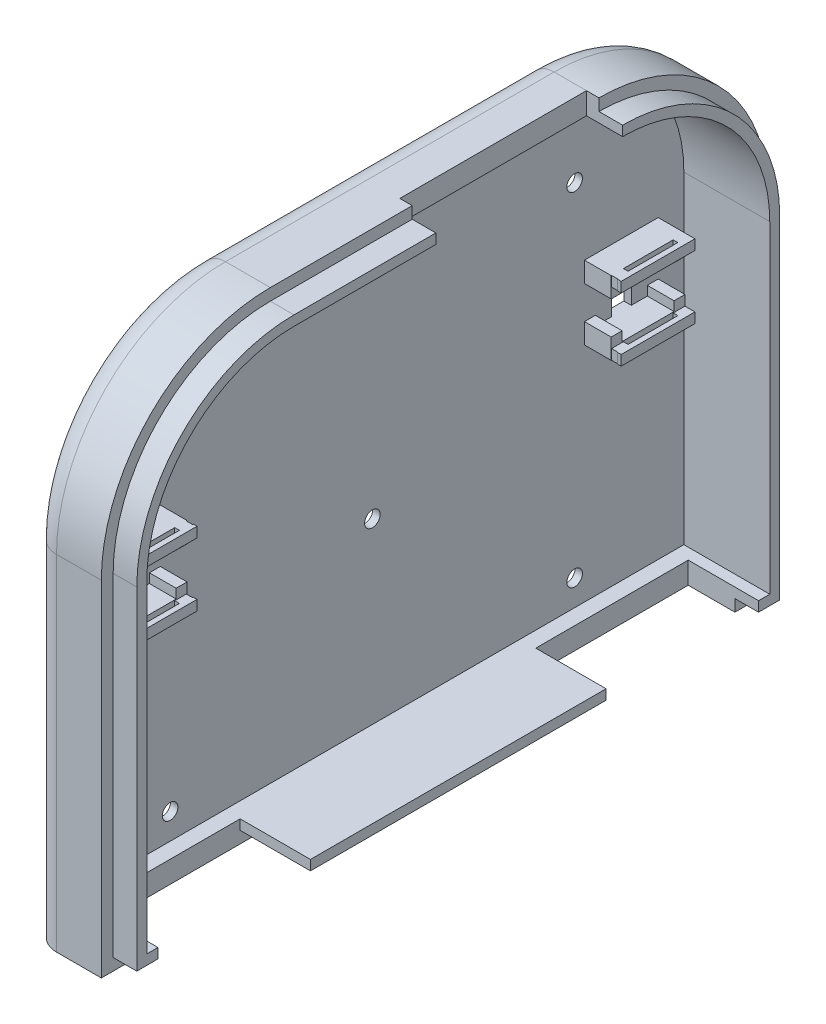
SolidWorks part; units mm, degrees
ref_plane "Front Plane" through (0, 0, 0) normal (0, 0, 1) x (1, 0, 0)
ref_plane "Top Plane" through (0, 0, 0) normal (0, 1, 0) x (1, 0, 0)
ref_plane "Right Plane" through (0, 0, 0) normal (1, 0, 0) x (0, 0, -1)
sketch "Sketch1" plane through (0, 0, 0) normal (1, 0, 0) x (0, 0, -1)
  line L0 (-52.8, 94.65) -> (52.8, 94.65)
  line L1 (-107.1, 40.35) -> (-107.1, -40.35)
  line L2 (-70, -70.35) -> (70, -70.35)
  line L3 (107.1, 40.35) -> (107.1, -40.35)
  line L4 (107.1, 0) -> (-107.1, 0) construction
  line L5 (0, 94.65) -> (0, -70.35) construction
  line L11 (107.1, -40.35) -> (107.1, -70.35)
  line L12 (107.1, -70.35) -> (70, -70.35)
  line L13 (-83.2, 28.3) -> (-76.8, 28.3)
  line L14 (-83.2, 28.3) -> (-83.2, 11.7)
  line L15 (-83.2, 11.7) -> (-76.8, 11.7)
  line L16 (-76.8, 28.3) -> (-76.8, 11.7)
  line L17 (-83.2, 28.3) -> (-76.8, 11.7) construction
  line L18 (-83.2, 11.7) -> (-76.8, 28.3) construction
  line L19 (76.8, 28.3) -> (83.2, 28.3)
  line L20 (76.8, 28.3) -> (76.8, 11.7)
  line L21 (76.8, 11.7) -> (83.2, 11.7)
  line L22 (83.2, 28.3) -> (83.2, 11.7)
  line L23 (76.8, 28.3) -> (83.2, 11.7) construction
  line L24 (76.8, 11.7) -> (83.2, 28.3) construction
  line L25 (80, 20) -> (-80, 20)
  line L27 (-107.1, -40.35) -> (-107.1, -70.35)
  line L28 (-107.1, -70.35) -> (-70, -70.35)
  arc A0 (52.8, 94.65) -> (107.1, 40.35) centre (52.8, 40.35) cw
  arc A1 (-52.8, 94.65) -> (-107.1, 40.35) centre (-52.8, 40.35) ccw
  point P16 (0, 0)
  point P17 (-80, 20)
  point P32 (80, 20)
  point P39 (-80, 20)
  point P40 (0, 20)
  dimension "D4" = 54.3
  dimension "D2" = 165
  dimension "D3" = 214.2
  dimension "D5" = 140
  dimension "D6" = 30
  dimension "D7" = 160
  dimension "D8" = 6.4
  dimension "D9" = 16.6
  dimension "D10" = 6.4
  dimension "D11" = 16.6
  dimension "D12" = 20
extrude "Boss-Extrude1" add sketch "Sketch1" along normal blind 2.4 contours L2 L3 A0 L0 A1 L1 L19 L22 L21 L20 L13 L16 L15 L14 region at (0, 9.471, 0)
sketch "Sketch9" plane through (2.4, 0, 0) normal (1, 0, 0) x (0, 0, -1)
  line L17 (52.8, 94.65) -> (-52.8, 94.65)
  line L31 (52.8, 94.65) -> (-52.8, 94.65)
  line L32 (-107.1, 40.35) -> (-107.1, -70.35)
  line L33 (-107.1, 40.35) -> (-107.1, -70.35)
  line L34 (-107.1, -70.35) -> (107.1, -70.35)
  line L39 (107.1, -70.35) -> (107.1, 40.35)
  line L43 (107.1, -70.35) -> (107.1, 40.35)
  line L45 (-107.1, -70.35) -> (107.1, -70.35)
  arc A15 (-52.8, 94.65) -> (-107.1, 40.35) centre (-52.8, 40.35) ccw
  arc A16 (-52.8, 94.65) -> (-107.1, 40.35) centre (-52.8, 40.35) ccw
  arc A17 (107.1, 40.35) -> (52.8, 94.65) centre (52.8, 40.35) ccw
  arc A18 (107.1, 40.35) -> (52.8, 94.65) centre (52.8, 40.35) ccw
  dimension "D1" = 0
sketch "Sketch10" plane through (2.4, 0, 0) normal (1, 0, 0) x (0, 0, -1)
  line L0 (65, -55.05) -> (0, -55.05) construction
  line L1 (-65, -55.05) -> (65, -55.05) construction
  line L2 (-65, -55.05) -> (-65, 54.95) construction
  line L3 (-65, 54.95) -> (65, 54.95) construction
  line L4 (65, -55.05) -> (65, 54.95) construction
  line L5 (-65, -55.05) -> (65, 54.95) construction
  line L6 (-65, 54.95) -> (65, -55.05) construction
  line L7 (0, -55.05) -> (-65, -55.05) construction
  line L8 (-107.1, -70.35) -> (107.1, -70.35) construction
  line L9 (0, -0.05) -> (0, 0) construction
  line L10 (0, -0.05) -> (0, -6.1) construction
  circle A4 centre (65, 54.95) radius 2.5
  circle A5 centre (65, -55.05) radius 2.5
  circle A6 centre (-65, -55.05) radius 2.5
  circle A7 centre (-65, 54.95) radius 2.5
  circle A11 centre (0, -6.1) radius 2.5
  point P0 (0, -0.05)
  point P11 (0, -55.05)
  point P12 (32.5, -55.05)
  point P14 (-32.5, -55.05)
  dimension "D3" = 5
  dimension "D4" = 15.3
  dimension "D1" = 130
  dimension "D2" = 110
  dimension "D5" = 6.05
extrude "Cut-Extrude1" cut sketch "Sketch10" against normal blind 100 and the other way blind 1000
sketch "Sketch12" plane through (2.4, 0, 0) normal (1, 0, 0) x (0, 0, -1)
  line L5 (-88.35, 11.7) -> (-88.35, 14.7)
  line L6 (-88.35, 11.7) -> (-88.35, 28.3) construction
  line L22 (71.65, 11.7) -> (71.65, 14.7)
  line L23 (71.65, 11.7) -> (71.65, 28.3) construction
  line L24 (71.65, 11.7) -> (88.35, 11.7) construction
  line L25 (88.35, 11.7) -> (88.35, 28.3) construction
  line L26 (71.65, 28.3) -> (88.35, 28.3) construction
  line L27 (71.65, 11.7) -> (88.35, 28.3) construction
  line L28 (88.35, 11.7) -> (71.65, 28.3) construction
  line L29 (71.65, 28.3) -> (71.65, 25.3)
  line L30 (88.35, 11.7) -> (88.35, 14.7)
  line L31 (88.35, 28.3) -> (88.35, 25.3)
  line L32 (71.65, 28.3) -> (88.35, 28.3)
  line L33 (88.35, 11.7) -> (71.65, 11.7)
  line L34 (88.35, 14.7) -> (91.85, 14.7)
  line L35 (71.65, 14.7) -> (68.15, 14.7)
  line L36 (68.15, 14.7) -> (68.15, 8.2)
  line L37 (68.15, 8.2) -> (91.85, 8.2)
  line L38 (91.85, 8.2) -> (91.85, 14.7)
  line L39 (71.65, 25.3) -> (68.15, 25.3)
  line L40 (68.15, 25.3) -> (68.15, 31.8)
  line L41 (68.15, 31.8) -> (91.85, 31.8)
  line L42 (91.85, 31.8) -> (91.85, 25.3)
  line L43 (91.85, 25.3) -> (88.35, 25.3)
  line L44 (83.2, 11.7) -> (76.8, 28.3) construction
  line L45 (83.2, 28.3) -> (76.8, 11.7) construction
  line L46 (-88.35, 11.7) -> (-71.65, 11.7) construction
  line L47 (-71.65, 11.7) -> (-71.65, 28.3) construction
  line L48 (-88.35, 28.3) -> (-71.65, 28.3) construction
  line L49 (-88.35, 11.7) -> (-71.65, 28.3) construction
  line L50 (-71.65, 11.7) -> (-88.35, 28.3) construction
  line L51 (-88.35, 28.3) -> (-88.35, 25.3)
  line L52 (-71.65, 11.7) -> (-71.65, 14.7)
  line L53 (-71.65, 28.3) -> (-71.65, 25.3)
  line L54 (-88.35, 28.3) -> (-71.65, 28.3)
  line L55 (-71.65, 11.7) -> (-88.35, 11.7)
  line L56 (-71.65, 14.7) -> (-68.15, 14.7)
  line L57 (-88.35, 14.7) -> (-91.85, 14.7)
  line L58 (-91.85, 14.7) -> (-91.85, 8.2)
  line L59 (-91.85, 8.2) -> (-68.15, 8.2)
  line L60 (-68.15, 8.2) -> (-68.15, 14.7)
  line L61 (-88.35, 25.3) -> (-91.85, 25.3)
  line L62 (-91.85, 25.3) -> (-91.85, 31.8)
  line L63 (-91.85, 31.8) -> (-68.15, 31.8)
  line L64 (-68.15, 31.8) -> (-68.15, 25.3)
  line L65 (-68.15, 25.3) -> (-71.65, 25.3)
  line L66 (-76.8, 11.7) -> (-83.2, 28.3) construction
  line L67 (-83.2, 11.7) -> (-76.8, 28.3) construction
  point P3 (-0.1438, 64.1533)
  point P4 (-80, 20)
  point P19 (80, 20)
  point P21 (-80, 20)
  point P30 (380.6447, 32.9453)
  point P31 (130.7088, -20.4974)
  point P32 (80, 20)
  point P49 (169.9078, -49.5925)
  dimension "D3" = 16.7
  dimension "D4" = 16.6
  dimension "D5" = 10.6
  dimension "D6" = 3.5
  dimension "D7" = 3.5
  dimension "D8" = 3.5
  dimension "D9" = 3.5
  dimension "D10" = 4.9497
  dimension "D11" = 16.7
  dimension "D12" = 16.6
  dimension "D13" = 10.6
  dimension "D14" = 3.5
  dimension "D15" = 3.5
  dimension "D16" = 3.5
  dimension "D17" = 3.5
  dimension "D18" = 4.9497
  dimension "D19" = 4.9497
  dimension "D20" = 7.3824
  dimension "D21" = 23.5468
  dimension "D22" = 24.088
  dimension "D23" = 4.9497
  dimension "D24" = 7.3824
  dimension "D25" = 23.5468
  dimension "D26" = 24.088
extrude "Boss-Extrude2" add sketch "Sketch12" along normal blind 8.6
sketch "Sketch14" plane through (11, 0, 0) normal (1, 0, 0) x (0, 0, -1)
  line L0 (-91.85, 31.8) -> (-91.85, 25.3) construction
  line L1 (-91.85, 31.8) -> (-68.15, 31.8)
  line L2 (-91.85, 31.8) -> (-91.85, 28.55)
  line L3 (-91.85, 28.55) -> (-68.15, 28.55)
  line L4 (-68.15, 31.8) -> (-68.15, 28.55)
  line L5 (-68.15, 31.8) -> (-91.85, 31.8) construction
  line L6 (-68.15, 25.3) -> (-68.15, 31.8) construction
  line L7 (-68.15, 8.2) -> (-68.15, 14.7) construction
  line L8 (-91.85, 8.2) -> (-68.15, 8.2)
  line L9 (-91.85, 8.2) -> (-91.85, 11.45)
  line L10 (-91.85, 11.45) -> (-68.15, 11.45)
  line L11 (-68.15, 8.2) -> (-68.15, 11.45)
  line L12 (91.85, 8.2) -> (91.85, 14.7) construction
  line L13 (68.15, 8.2) -> (91.85, 8.2)
  line L14 (68.15, 8.2) -> (68.15, 11.45)
  line L15 (68.15, 11.45) -> (91.85, 11.45)
  line L16 (91.85, 8.2) -> (91.85, 11.45)
  line L17 (91.85, 25.3) -> (91.85, 31.8) construction
  line L18 (68.15, 31.8) -> (91.85, 31.8)
  line L19 (68.15, 31.8) -> (68.15, 28.55)
  line L20 (68.15, 28.55) -> (91.85, 28.55)
  line L21 (91.85, 31.8) -> (91.85, 28.55)
extrude "Boss-Extrude3" add sketch "Sketch14" along normal blind 3.2
sketch "Sketch16" plane through (0, 28.55, 0) normal (0, -1, 0) x (1, 0, 0)
  line L0 (11, 91.85) -> (11, 68.15) construction
  line L1 (11, 68.3952) -> (12.9651, 68.3952)
  line L2 (11, 68.3952) -> (11, 51.6632)
  line L3 (11, 51.6632) -> (12.9651, 51.6632)
  line L4 (12.9651, 68.3952) -> (12.9651, 51.6632)
  line L5 (11, -68.15) -> (11, -91.85) construction
  line L6 (11, -51.6659) -> (12.9651, -51.6659)
  line L7 (11, -51.6659) -> (11, -68.2634)
  line L8 (11, -68.2634) -> (12.9651, -68.2634)
  line L9 (12.9651, -51.6659) -> (12.9651, -68.2634)
extrude "Cut-Extrude2" cut sketch "Sketch16" against normal blind 100 and the other way blind 100
sketch "Sketch17" plane through (0, 0, 0) normal (1, 0, 0) x (0, 0, -1)
  line L0 (-103.9, 40.35) -> (-103.9, -67.15) construction
  line L1 (-103.9, -67.15) -> (103.9, -67.15) construction
  line L2 (103.9, -67.15) -> (103.9, 40.35) construction
  line L3 (52.8, 91.45) -> (-52.8, 91.45) construction
  line L4 (52.8, 94.65) -> (-52.8, 94.65)
  line L5 (-107.1, 40.35) -> (-107.1, -70.35)
  line L6 (-107.1, -70.35) -> (107.1, -70.35)
  line L7 (107.1, -70.35) -> (107.1, 40.35)
  line L8 (52.8, 94.65) -> (-52.8, 94.65) construction
  line L9 (-107.1, 40.35) -> (-107.1, -70.35) construction
  line L11 (107.1, -70.35) -> (107.1, 40.35) construction
  line L16 (100.1, -63.35) -> (100.1, 40.35)
  line L17 (52.8, 87.65) -> (-52.8, 87.65)
  line L18 (-100.1, 40.35) -> (-100.1, -63.35)
  line L19 (-100.1, -63.35) -> (100.1, -63.35)
  line L24 (52.8, 90.85) -> (-52.8, 90.85)
  line L25 (-103.3, 40.35) -> (-103.3, -66.55)
  line L27 (103.3, -66.55) -> (103.3, 40.35)
  line L28 (-107.1, -70.35) -> (107.1, -70.35) construction
  line L29 (-103.3, -66.55) -> (103.3, -66.55) construction
  line L31 (-103.3, -66.55) -> (103.3, -66.55)
  arc A0 (103.9, 40.35) -> (52.8, 91.45) centre (52.8, 40.35) ccw construction
  arc A1 (-52.8, 91.45) -> (-103.9, 40.35) centre (-52.8, 40.35) ccw construction
  arc A2 (-52.8, 94.65) -> (-107.1, 40.35) centre (-52.8, 40.35) ccw
  arc A3 (107.1, 40.35) -> (52.8, 94.65) centre (52.8, 40.35) ccw
  arc A4 (-52.8, 94.65) -> (-107.1, 40.35) centre (-52.8, 40.35) ccw construction
  arc A5 (107.1, 40.35) -> (52.8, 94.65) centre (52.8, 40.35) ccw construction
  arc A8 (100.1, 40.35) -> (52.8, 87.65) centre (52.8, 40.35) ccw
  arc A9 (-52.8, 87.65) -> (-100.1, 40.35) centre (-52.8, 40.35) ccw
  arc A12 (-52.8, 90.85) -> (-103.3, 40.35) centre (-52.8, 40.35) ccw
  arc A13 (103.3, 40.35) -> (52.8, 90.85) centre (52.8, 40.35) ccw
  dimension "D4" = 157.4
  dimension "D5" = 206.6
  dimension "D7" = 207.8
  dimension "D8" = 214.2
  dimension "D9" = 3.2
  dimension "D2" = 3.2
  dimension "D10" = 3.2
  dimension "D11" = 3.2
  dimension "D1" = 0
  dimension "D3" = 3.2
  dimension "D6" = 0.6
extrude "Boss-Extrude4" add sketch "Sketch17" along normal blind 30
sketch "Sketch21" plane through (2.4, 0, 0) normal (1, 0, 0) x (0, 0, -1)
  line L4 (-107.1, -70.35) -> (107.1, -70.35)
  line L6 (-107.1, -70.35) -> (107.1, -70.35)
  line L8 (52.8, 94.65) -> (-52.8, 94.65)
  line L9 (-107.1, 40.35) -> (-107.1, -70.35)
  line L11 (107.1, -70.35) -> (107.1, 40.35)
  line L12 (52.8, 94.65) -> (-52.8, 94.65)
  line L13 (-107.1, 40.35) -> (-107.1, -70.35)
  line L15 (107.1, -70.35) -> (107.1, 40.35)
  arc A4 (-52.8, 94.65) -> (-107.1, 40.35) centre (-52.8, 40.35) ccw
  arc A5 (107.1, 40.35) -> (52.8, 94.65) centre (52.8, 40.35) ccw
  arc A6 (-52.8, 94.65) -> (-107.1, 40.35) centre (-52.8, 40.35) ccw
  arc A7 (107.1, 40.35) -> (52.8, 94.65) centre (52.8, 40.35) ccw
  dimension "D1" = 0
sketch "Sketch22" plane through (2.4, 0, 0) normal (1, 0, 0) x (0, 0, -1)
  line L0 (-107.1, -70.35) -> (107.1, -70.35) construction
  line L1 (-107.1, -70.35) -> (107.1, -70.35)
  line L21 (52.8, 94.65) -> (-52.8, 94.65)
  line L22 (107.1, -70.35) -> (107.1, 40.35)
  line L24 (-107.1, 40.35) -> (-107.1, -70.35)
  line L25 (52.8, 94.65) -> (-52.8, 94.65)
  line L26 (107.1, -70.35) -> (107.1, 40.35)
  line L28 (-107.1, 40.35) -> (-107.1, -70.35)
  line L44 (-103.3, -66.55) -> (103.3, -66.55)
  line L45 (103.3, -66.55) -> (103.3, 40.35)
  line L46 (52.8, 90.85) -> (-52.8, 90.85)
  line L47 (-103.3, 40.35) -> (-103.3, -66.55)
  line L48 (-103.3, -66.55) -> (103.3, -66.55)
  line L49 (103.3, -66.55) -> (103.3, 40.35)
  line L50 (52.8, 90.85) -> (-52.8, 90.85)
  line L51 (-103.3, 40.35) -> (-103.3, -66.55)
  arc A6 (-52.8, 94.65) -> (-107.1, 40.35) centre (-52.8, 40.35) ccw
  arc A7 (107.1, 40.35) -> (52.8, 94.65) centre (52.8, 40.35) ccw
  arc A8 (-52.8, 94.65) -> (-107.1, 40.35) centre (-52.8, 40.35) ccw
  arc A9 (107.1, 40.35) -> (52.8, 94.65) centre (52.8, 40.35) ccw
  arc A20 (103.3, 40.35) -> (52.8, 90.85) centre (52.8, 40.35) ccw
  arc A21 (-52.8, 90.85) -> (-103.3, 40.35) centre (-52.8, 40.35) ccw
  arc A22 (103.3, 40.35) -> (52.8, 90.85) centre (52.8, 40.35) ccw
  arc A23 (-52.8, 90.85) -> (-103.3, 40.35) centre (-52.8, 40.35) ccw
  dimension "D1" = 0
  dimension "D2" = 0
extrude "Boss-Extrude7" add sketch "Sketch22" along normal blind 20
sketch "Sketch23" plane through (0, -70.35, 0) normal (0, -1, 0) x (1, 0, 0)
  line L0 (0, 99.1) -> (0, 107.1)
  line L1 (0, 107.1) -> (8, 107.1)
  line L2 (8, -107.1) -> (0, -107.1)
  line L3 (0, -107.1) -> (0, -99.1)
  line L8 (0, 107.1) -> (0, -107.1)
  line L9 (0, -107.1) -> (22.4, -107.1)
  line L10 (22.4, -107.1) -> (22.4, 107.1)
  line L11 (22.4, 107.1) -> (0, 107.1)
  line L12 (0, 99.1) -> (0, -99.1) construction
  line L13 (8, -107.1) -> (22.4, -107.1) construction
  line L15 (22.4, 107.1) -> (8, 107.1) construction
  arc A0 (0, 99.1) -> (8, 107.1) centre (8, 99.1) cw
  arc A1 (0, -99.1) -> (8, -107.1) centre (8, -99.1) ccw
  dimension "D2" = 8
  dimension "D1" = 0
extrude "Cut-Extrude4" cut sketch "Sketch23" against normal through all
fillet "Fillet4" radius 8 5 edges at (0, 87.7258, 79.3335) (0, 94.65, 0) (0, 87.7258, -79.3335) (1.5353, 58.957, 103.8124) (1.5353, 58.957, -103.8124)
sketch "Sketch26" plane through (22.4, 0, 0) normal (1, 0, 0) x (0, 0, -1)
  line L1 (-47.5, -63.3365) -> (47.5, -63.3365)
  line L2 (47.5, -63.3365) -> (47.5, -66.55)
  line L6 (47.5, -66.55) -> (-47.5, -66.55)
  line L7 (-47.5, -66.55) -> (-47.5, -63.3365)
  line L8 (-103.3, -66.55) -> (103.3, -66.55) construction
  line L9 (-96.5, -74.5369) -> (96.5, -74.5369)
  line L10 (-96.5, -74.5369) -> (-96.5, -58.5631)
  line L11 (-96.5, -58.5631) -> (96.5, -58.5631)
  line L12 (96.5, -74.5369) -> (96.5, -58.5631)
  line L13 (-96.5, -74.5369) -> (96.5, -58.5631) construction
  line L14 (-96.5, -58.5631) -> (96.5, -74.5369) construction
  line L15 (107.1, -70.35) -> (107.1, 40.35) construction
  point P0 (0, -66.55)
  point P9 (0, -63.3365)
  point P13 (0, -63.3365)
  point P16 (0, -63.3365)
  dimension "D1" = 10.6
  dimension "D2" = 15.9739
  dimension "D3" = 95
  dimension "D4" = 3.2135
extrude "Cut-Extrude7" cut sketch "Sketch26" against normal blind 15 and the other way blind 20
sketch "Sketch28" plane through (0, 94.65, 0) normal (0, 1, 0) x (1, 0, 0)
  line L0 (22.4, 52.8) -> (18.4, 52.8)
  line L1 (22.4, 52.8) -> (8, 52.8) construction
  line L2 (18.4, 52.8) -> (18.4, -7.2)
  line L3 (18.4, -7.2) -> (53.1003, -7.2)
  line L4 (53.1003, -7.2) -> (53.1003, 52.8)
  line L5 (53.1003, 52.8) -> (22.4, 52.8)
  dimension "D1" = 4
  dimension "D2" = 60
extrude "Cut-Extrude8" cut sketch "Sketch28" against normal blind 10
sketch "Sketch29" plane through (0, 28.55, 0) normal (0, -1, 0) x (1, 0, 0)
  line L5 (11, 91.85) -> (11, 68.3952) construction
  line L7 (11, 88.1226) -> (11, 72.1226)
  line L8 (11, 72.1226) -> (12.5, 72.1226)
  line L9 (12.5, 72.1226) -> (12.5, 88.1226)
  line L10 (12.5, 88.1226) -> (11, 88.1226)
  line L12 (11, -68.2634) -> (11, -91.85) construction
  line L13 (11, -72.0567) -> (11, -88.0567)
  line L14 (11, -88.0567) -> (12.5, -88.0567)
  line L15 (12.5, -88.0567) -> (12.5, -72.0567)
  line L16 (12.5, -72.0567) -> (11, -72.0567)
  point P0 (11, 80.1226)
  point P1 (11, -80.0567)
  point P6 (11, 80.1226)
  point P9 (11, -80.0567)
  point P14 (11, -80.0567)
  dimension "D1" = 16
  dimension "D2" = 1.5
  dimension "D3" = 16
  dimension "D4" = 1.5
extrude "Cut-Extrude9" cut sketch "Sketch29" against normal blind 30 and the other way blind 1000
